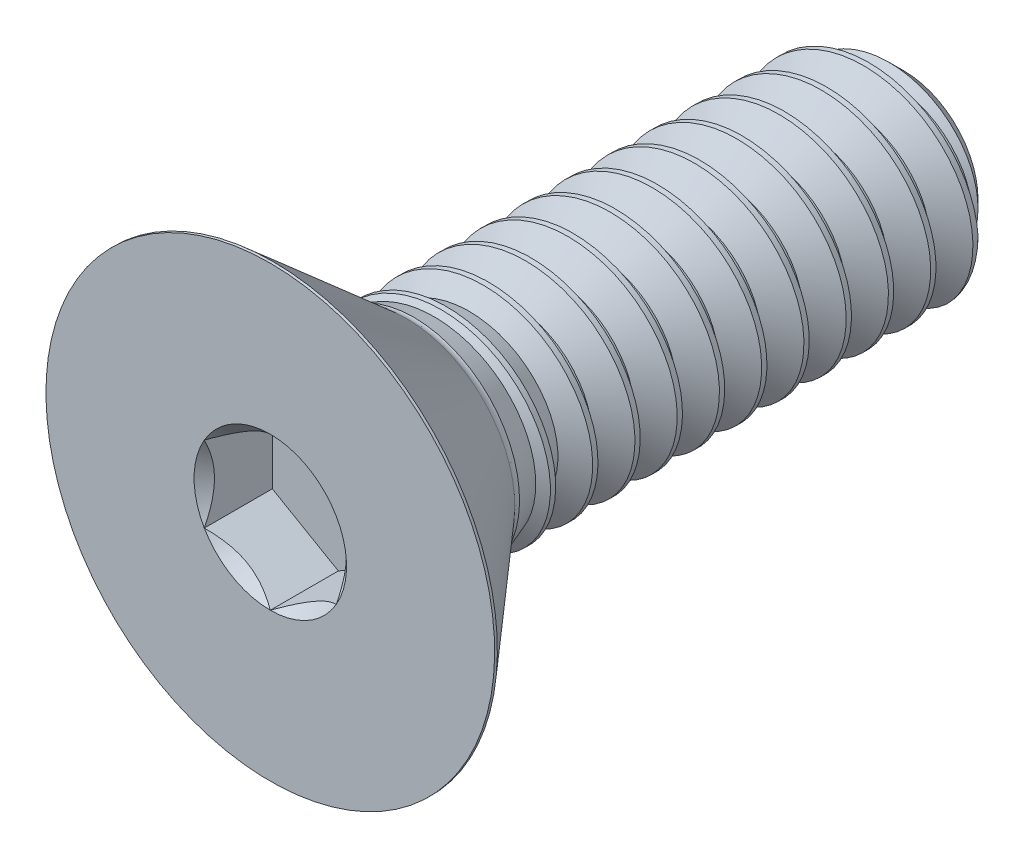
SolidWorks part; units mm, degrees
material "Alloy Steel (SS)"
ref_plane "Front Plane" through (0, 0, 0) normal (0, 0, 1) x (1, 0, 0)
ref_plane "Top Plane" through (0, 0, 0) normal (0, 1, 0) x (1, 0, 0)
ref_plane "Right Plane" through (0, 0, 0) normal (1, 0, 0) x (0, 0, -1)
sketch "Sketch1" plane through (0, 0, 0) normal (1, 0, 0) x (0, 0, -1)
  line L0 (-9.525, 0) -> (9.525, 0) construction
  line L1 (-9.525, 0) -> (-9.525, 6.7437)
  line L2 (-9.525, 6.7437) -> (-9.4432, 6.7437)
  line L3 (-9.4432, 6.7437) -> (-5.4356, 3.2599)
  line L4 (-9.4432, -6.7437) -> (-5.4356, -3.2599)
  line L5 (9.525, 0) -> (9.525, 3.175)
  line L6 (9.525, 3.175) -> (-5.4356, 3.175)
  line L7 (8.5725, 3.175) -> (9.525, 2.2225)
  line L8 (9.4456, 3.3125) -> (10.0806, 2.2126) construction
  line L9 (10.0806, 2.2126) -> (10.7156, 3.3125) construction
  line L10 (10.7156, 3.3125) -> (9.4456, 3.3125) construction
  line L11 (9.4853, 3.2437) -> (10.6759, 3.2437)
  line L12 (10.6759, 3.2437) -> (10.16, 2.3501)
  line L13 (10.16, 2.3501) -> (10.0012, 2.3501)
  line L14 (10.0012, 2.3501) -> (9.4853, 3.2437)
  line L15 (10.0806, 2.3501) -> (10.0806, 2.2126) construction
  line L16 (9.525, 3.175) -> (10.6363, 3.175) construction
  line L17 (10.0806, 3.3125) -> (10.0806, 3.175) construction
  line L18 (9.525, -3.175) -> (-5.4356, -3.175)
  arc A0 (-5.4356, 3.2599) -> (-5.2084, 3.175) centre (-5.2084, 3.5213) ccw
  point P2 (0, 0)
  point P23 (-7.4803, 0)
  point P27 (10.0806, 3.2437)
  point P30 (7.62, -3.175)
  point P31 (-5.4356, 6.7437)
  point P34 (-9.4432, -6.7437)
  dimension "Length" = 19.05
  dimension "Head Height" = 4.0894
  dimension "Head Diameter" = 13.4874
  dimension "Countersink Angle" = 82
  dimension "Screw Size Decimal Equivalent" = 6.35
  dimension "Pitch" = 1.27
  dimension "D4" = 0.1588
  dimension "D3" = 45
  dimension "D5" = 0.9525
  dimension "D6" = 2.0447
  dimension "D1" = 1.905
  dimension "D7" = 0.0818
sketch "Sketch8" plane through (0, 0, 0) normal (0, 0, 1) x (1, 0, 0)
  line L1 (0, 2.2914) -> (-1.9844, 1.1457)
  line L2 (-1.9844, 1.1457) -> (-1.9844, -1.1457)
  line L3 (-1.9844, -1.1457) -> (0, -2.2914)
  line L4 (0, -2.2914) -> (1.9844, -1.1457)
  line L5 (1.9844, -1.1457) -> (1.9844, 1.1457)
  line L6 (1.9844, 1.1457) -> (0, 2.2914)
  circle A0 centre (0, 0) radius 1.9844 construction
  dimension "Drive Size" = 3.9688
sketch "Sketch2" plane through (0, 0, 0) normal (1, 0, 0) x (0, 0, -1)
  line L0 (-9.4432, 6.7437) -> (-5.4356, 3.2599) construction
  line L1 (-9.525, 0) -> (-9.525, 6.7437) construction
  line L2 (-9.4432, 6.7437) -> (-5.4356, 3.2599)
  line L3 (-9.525, 0) -> (-9.525, 6.7437)
  line L4 (-9.525, 6.7437) -> (-9.4432, 6.7437) construction
  line L5 (-9.525, 6.7437) -> (-9.4432, 6.7437)
  line L6 (-5.2084, 3.175) -> (8.5725, 3.175)
  line L7 (8.5725, 3.175) -> (9.525, 2.2225)
  line L8 (9.525, 2.2225) -> (9.525, 0)
  line L9 (9.525, 0) -> (-9.525, 0)
  arc A0 (-5.4356, 3.2599) -> (-5.2084, 3.175) centre (-5.2084, 3.5213) ccw construction
  arc A1 (-5.4356, 3.2599) -> (-5.2084, 3.175) centre (-5.2084, 3.5213) ccw
revolve "Revolve1" add sketch "Sketch2" angle 360 about L9
sketch "Sketch9" plane through (0, 0, 9.525) normal (0, 0, 1) x (1, 0, 0)
  line L0 (1.9844, -1.1457) -> (1.9844, 1.1457) construction
  line L1 (0, -2.2914) -> (1.9844, -1.1457) construction
  line L2 (-1.9844, -1.1457) -> (0, -2.2914) construction
  line L3 (-1.9844, 1.1457) -> (-1.9844, -1.1457) construction
  line L4 (0, 2.2914) -> (-1.9844, 1.1457) construction
  line L5 (1.9844, 1.1457) -> (0, 2.2914) construction
  line L6 (1.9844, -1.1457) -> (1.9844, 1.1457)
  line L7 (0, -2.2914) -> (1.9844, -1.1457)
  line L8 (-1.9844, -1.1457) -> (0, -2.2914)
  line L9 (-1.9844, 1.1457) -> (-1.9844, -1.1457)
  line L10 (0, 2.2914) -> (-1.9844, 1.1457)
  line L11 (1.9844, 1.1457) -> (0, 2.2914)
sketch "Sketch10" plane through (0, 0, 9.525) normal (0, 0, 1) x (1, 0, 0)
  circle A0 centre (0, 0) radius 2.2914
extrude "Cut-Extrude2" cut sketch "Sketch10" against normal up to vertex (2.0447 mm away) draft 45 up to point (0, 0, 7.4803)
extrude "Cut-Extrude1" cut sketch "Sketch9" against normal up to vertex (2.0447 mm away) up to point (0, 0, 7.4803)
ref_plane "Plane1" through (0, 0, 5.2084) normal (0, 0, 1) x (1, 0, 0)
split "Split1" trim tools "Plane1" bodies to split 111 resulting bodies 105 106
sketch "Sketch3" plane through (0, 0, -9.525) normal (0, 0, -1) x (-1, 0, 0)
  circle A0 centre (0, 0) radius 3.175 construction
  circle A1 centre (0, 0) radius 3.175
curve "Helix/Spiral1" pitch 1.27 height 19.05 turns 15
sketch "Sketch4" plane through (0, 0, 0) normal (1, 0, 0) x (0, 0, -1)
  line L0 (9.4853, 3.2437) -> (10.6759, 3.2437) construction
  line L1 (10.0012, 2.3501) -> (9.4853, 3.2437) construction
  line L2 (10.16, 2.3501) -> (10.0012, 2.3501) construction
  line L3 (10.6759, 3.2437) -> (10.16, 2.3501) construction
  line L4 (9.4853, 3.2437) -> (10.6759, 3.2437)
  line L5 (10.0012, 2.3501) -> (9.4853, 3.2437)
  line L6 (10.16, 2.3501) -> (10.0012, 2.3501)
  line L7 (10.6759, 3.2437) -> (10.16, 2.3501)
sweep "Cut-Sweep1" cut profiles "Sketch4" path "Helix/Spiral1" align with end faces yes
sketch "Sketch7" plane through (0, 0, 5.2084) normal (0, 0, 1) x (1, 0, 0)
  circle A0 centre (0, 0) radius 3.175
extrude "Boss-Extrude2" add sketch "Sketch7" against normal up to next (14.7334 mm away) draft 20
equation "\"D4@Sketch1\" = \"Pitch@Sketch1\" / 8"
equation "\"D5@Sketch1\"=\"Pitch@Sketch1\"*0.75"
equation "\"D4@Helix/Spiral1\"=\"Pitch@Sketch1\""
equation "\"D3@Helix/Spiral1\"=\"Length@Sketch1\""
equation "\"D6@Sketch1\"=\"Head Height@Sketch1\"/2"
equation "\"D1@Sketch1\"=\"Pitch@Sketch1\"*1.5"
equation "\"D7@Sketch1\"=\"Head Height@Sketch1\"*0.02"
